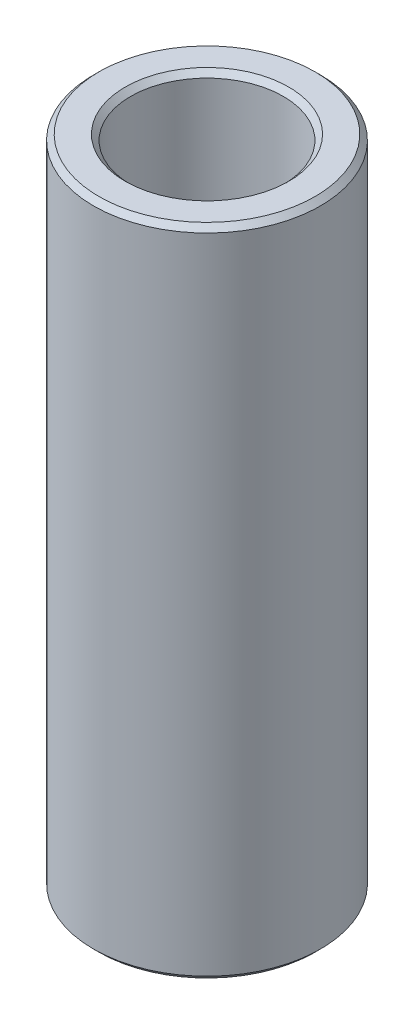
SolidWorks part; units mm, degrees
ref_plane "Front Plane" through (0, 0, 0) normal (0, 0, 1) x (1, 0, 0)
ref_plane "Top Plane" through (0, 0, 0) normal (0, 1, 0) x (1, 0, 0)
ref_plane "Right Plane" through (0, 0, 0) normal (1, 0, 0) x (0, 0, -1)
sketch "Sketch1" plane through (0, 0, 0) normal (0, 1, 0) x (1, 0, 0)
  circle A0 centre (0, 0) radius 57.5
  dimension "SLEEVE_OD" = 115
extrude "Boss-Extrude1" add sketch "Sketch1" along normal blind 331.6191
sketch "Sketch2" plane through (0, 0, 0) normal (0, 1, 0) x (1, 0, 0)
  circle A0 centre (0, 0) radius 38.6831
  dimension "BORE_D" = 77.3662
extrude "Cut-Extrude1" cut sketch "Sketch2" along normal through all
chamfer "Chamfer1" distance 2.74 angle 45 4 edges at (0, 331.6191, 38.6831) (0, 0, 38.6831) (0, 0, 57.5) (0, 331.6191, 57.5)
